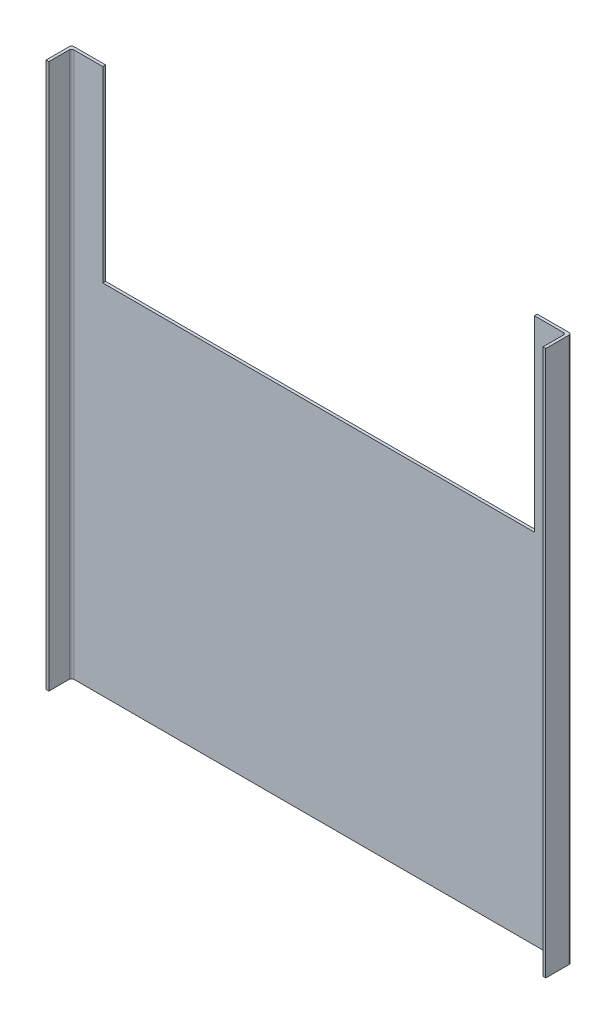
SolidWorks part; units mm, degrees
ref_plane "Front Plane" through (0, 0, 0) normal (0, 0, 1) x (1, 0, 0)
ref_plane "Top Plane" through (0, 0, 0) normal (0, 1, 0) x (1, 0, 0)
ref_plane "Right Plane" through (0, 0, 0) normal (1, 0, 0) x (0, 0, -1)
sketch "Sketch1" plane through (0, 0, 0) normal (0, 0, 1) x (1, 0, 0)
  line L0 (1041.4, 1219.2) -> (1117.6, 1219.2)
  line L1 (0, 0) -> (1117.6, 0)
  line L2 (0, 0) -> (0, 1219.2)
  line L3 (0, 1219.2) -> (76.2, 1219.2)
  line L4 (1117.6, 0) -> (1117.6, 1219.2)
  line L6 (76.2, 1219.2) -> (76.2, 800)
  line L7 (76.2, 800) -> (1041.4, 800)
  line L8 (1041.4, 1219.2) -> (1041.4, 800)
  dimension "D1" = 1117.6
  dimension "D2" = 1219.2
  dimension "D3" = 76.2
  dimension "D4" = 76.2
  dimension "D5" = 419.2
extrude "Boss-Extrude1" add sketch "Sketch1" along normal blind 6.35 contours L3 L6 L7 L8 L0 L4 L1 L2
sketch "Sketch2" plane through (0, 0, 6.35) normal (0, 0, 1) x (1, 0, 0)
  line L0 (0, 0) -> (1117.6, 0) construction
  line L1 (0, 1219.2) -> (6.35, 1219.2)
  line L2 (0, 1219.2) -> (0, 0)
  line L3 (0, 0) -> (6.35, 0)
  line L4 (6.35, 1219.2) -> (6.35, 0)
  line L6 (1117.6, 1219.2) -> (1111.25, 1219.2)
  line L7 (1117.6, 1219.2) -> (1117.6, 0)
  line L8 (1117.6, 0) -> (1111.25, 0)
  line L9 (1111.25, 1219.2) -> (1111.25, 0)
  dimension "D1" = 6.35
extrude "Boss-Extrude2" add sketch "Sketch2" along normal blind 50.8
fillet "Fillet1" radius 5 4 edges at (1117.6, 609.6, 0) (0, 609.6, 0) (1111.25, 609.6, 6.35) (6.35, 609.6, 6.35)
